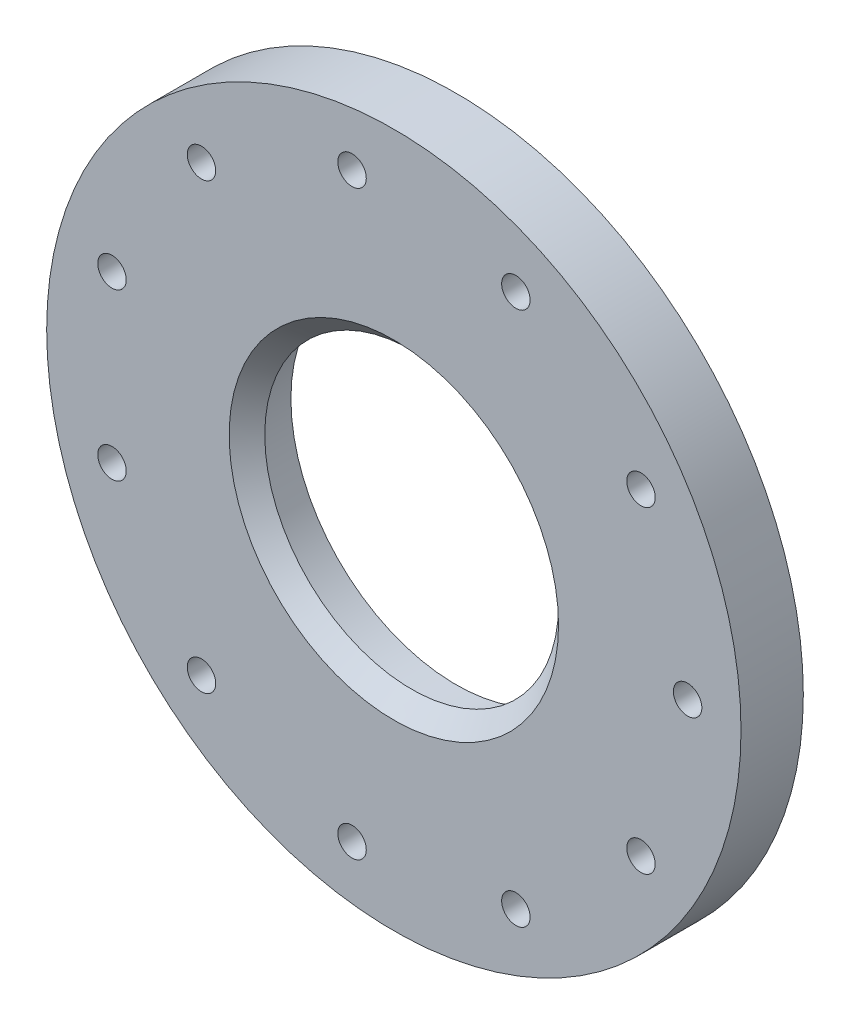
SolidWorks part; units mm, degrees
ref_plane "Front Plane" through (0, 0, 0) normal (0, 0, 1) x (1, 0, 0)
ref_plane "Top Plane" through (0, 0, 0) normal (0, 1, 0) x (1, 0, 0)
ref_plane "Right Plane" through (0, 0, 0) normal (1, 0, 0) x (0, 0, -1)
ref_plane "Plane1" through (0, 0, 15) normal (0, 0, 1) x (1, 0, 0)
sketch "Sketch1" plane through (0, 0, 15) normal (0, 0, 1) x (1, 0, 0)
  circle A0 centre (0, 0) radius 39
  circle A1 centre (0, 0) radius 33 construction
  circle A2 centre (33, 0) radius 2.5
  circle A3 centre (27.7614, -17.8411) radius 2.5
  circle A4 centre (13.7087, -30.0179) radius 2.5
  circle A5 centre (-4.6964, -32.6641) radius 2.5
  circle A6 centre (-21.6104, -24.9397) radius 2.5
  circle A7 centre (-31.6633, -9.2972) radius 2.5
  circle A8 centre (-31.6633, 9.2972) radius 2.5
  circle A9 centre (-21.6104, 24.9397) radius 2.5
  circle A10 centre (-4.6964, 32.6641) radius 2.5
  circle A11 centre (13.7087, 30.0179) radius 2.5
  circle A12 centre (27.7614, 17.8411) radius 2.5
  circle A13 centre (0, 0) radius 16
  point P28 (0, 0)
extrude "Boss-Extrude1" add sketch "Sketch1" along normal blind 7
sketch "Sketch2" plane through (0, 0, 15) normal (0, 0, -1) x (-1, 0, 0)
  circle A0 centre (0, 0) radius 18.5625
  dimension "D1" = 37.125
extrude "Cut-Extrude1" cut sketch "Sketch2" against normal blind 5
sketch "Sketch3" plane through (0, 0, 22) normal (0, 0, 1) x (1, 0, 0)
  circle A0 centre (-4.6964, 32.6641) radius 1.6
  circle A1 centre (-4.6964, 32.6641) radius 2.5
  circle A2 centre (13.7087, 30.0179) radius 2.5
  circle A3 centre (13.7087, 30.0179) radius 1.6
  circle A4 centre (27.7614, 17.8411) radius 2.5
  circle A5 centre (27.7614, 17.8411) radius 1.6
  circle A6 centre (33, 0) radius 2.5
  circle A7 centre (33, 0) radius 1.6
  circle A8 centre (27.7614, -17.8411) radius 2.5
  circle A9 centre (27.7614, -17.8411) radius 1.6
  circle A10 centre (13.7087, -30.0179) radius 2.5
  circle A11 centre (13.7087, -30.0179) radius 1.6
  circle A12 centre (-4.6964, -32.6641) radius 2.5
  circle A13 centre (-4.6964, -32.6641) radius 1.6
  circle A14 centre (-21.6104, -24.9397) radius 2.5
  circle A15 centre (-21.6104, -24.9397) radius 1.6
  circle A16 centre (-31.6633, -9.2972) radius 2.5
  circle A17 centre (-31.6633, -9.2972) radius 1.6
  circle A18 centre (-31.6633, 9.2972) radius 2.5
  circle A19 centre (-31.6633, 9.2972) radius 1.6
  circle A20 centre (-21.6104, 24.9397) radius 2.5
  circle A21 centre (-21.6104, 24.9397) radius 1.6
  point P5 (0, 0)
  point P6 (1.2547, -3.0229)
  point P36 (0, 0)
  point P37 (0, 0)
  dimension "D1" = 5
  dimension "D2" = 3.2
  dimension "D3" = 11
extrude "Boss-Extrude2" add sketch "Sketch3" against normal blind 4
chamfer "Chamfer1" distance 2.5 angle 45 1 edges at (16, 0, 22)
